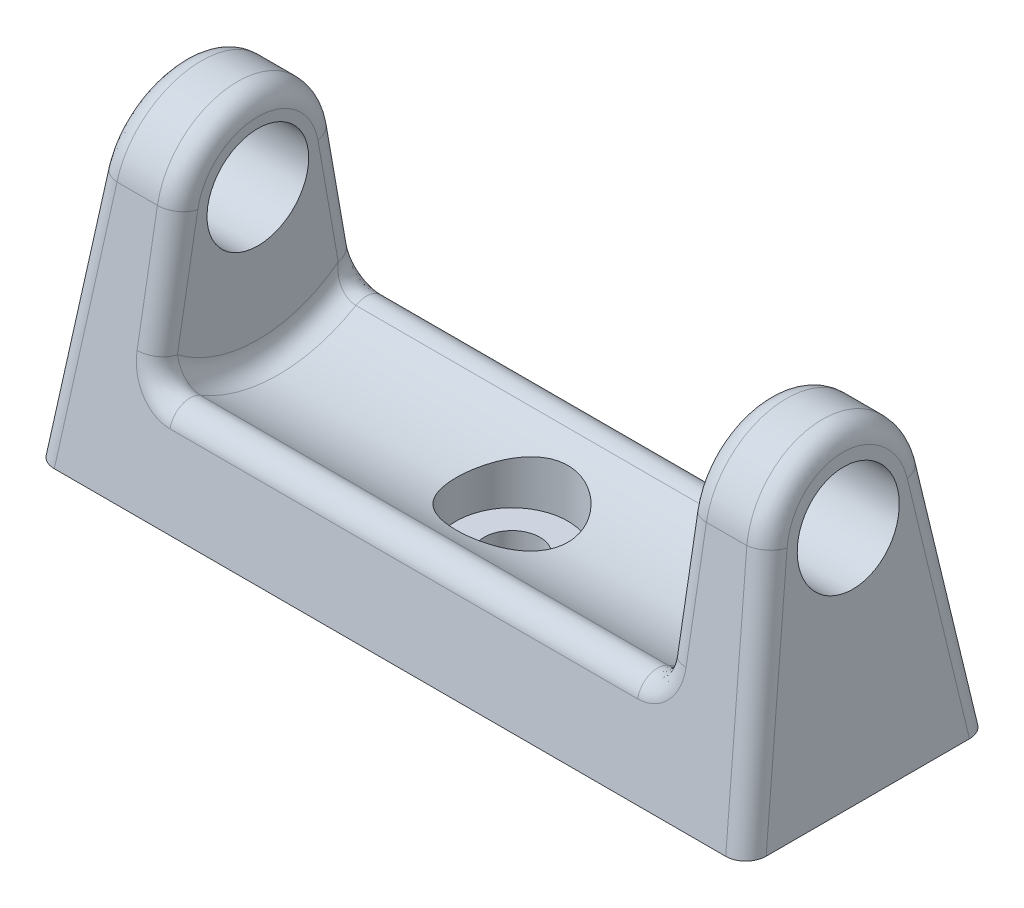
SolidWorks part; units mm, degrees
ref_plane "Front Plane" through (0, 0, 0) normal (0, 0, 1) x (1, 0, 0)
ref_plane "Top Plane" through (0, 0, 0) normal (0, 1, 0) x (1, 0, 0)
ref_plane "Right Plane" through (0, 0, 0) normal (1, 0, 0) x (0, 0, -1)
sketch "Sketch1" plane through (0, 0, 0) normal (1, 0, 0) x (0, 0, -1)
  line L0 (12, 0) -> (-12, 0)
  line L1 (-12, 0) -> (-7.8786, 23.3883)
  line L3 (7.8786, 23.3883) -> (12, 0)
  arc A0 (7.8786, 23.3883) -> (-7.8786, 23.3883) centre (0, 22) ccw
  circle A1 centre (0, 22) radius 5
  point P4 (0, 0)
  dimension "D1" = 22
  dimension "D2" = 10
  dimension "D3" = 16
  dimension "D5" = 24
extrude "Boss-Extrude1" add sketch "Sketch1" along normal mid plane 70
sketch "Sketch2" plane through (0, 0, 0) normal (1, 0, 0) x (0, 0, -1)
  circle A0 centre (0, 22) radius 15
  arc A1 (7.8786, 23.3883) -> (-7.8786, 23.3883) centre (0, 22) ccw construction
  dimension "D1" = 30
extrude "Cut-Extrude1" cut sketch "Sketch2" against normal mid plane 50
fillet "Fillet2" radius 2 10 edges at (25, 7, 0) (-25, 7, 0) (25, 17.1403, -8.9796) (25, 30, 0) (25, 17.1403, 8.9796) (-25, 17.1403, -8.9796) (-25, 30, 0) (-25, 17.1403, 8.9796) (0, 10.8923, 10.0806) (0, 10.8923, -10.0806)
sketch3d "3DSketch2" plane through (0, 0, 0) normal (0, 0, 1) x (1, 0, 0)
sketch "Sketch5" plane through (0, 7, 0) normal (0, -1, 0) x (-1, 0, 0)
  point P0 (0, 0)
sketch "Sketch8" plane through (0, 0, 0) normal (0, 0, 1) x (1, 0, 0)
  line L0 (-35, 30) -> (-35, 0)
  line L1 (-35, 30) -> (-35, 23.3883) construction
  line L2 (-27, 30) -> (-35, 30) construction
  line L3 (-35, 0) -> (-32.3753, 30)
  line L4 (-32.3753, 30) -> (-35, 30)
  line L5 (0, 0) -> (0, 30.0028) construction
  line L6 (35, 0) -> (-35, 0) construction
  line L7 (32.3753, 30) -> (35, 30)
  line L8 (35, 0) -> (32.3753, 30)
  line L9 (35, 30) -> (35, 0)
  point P15 (0, 0)
  dimension "D1" = 5
extrude "Cut-Extrude2" cut sketch "Sketch8" against normal through all both and the other way through all
fillet "Fillet5" radius 2 6 edges at (33.9769, 11.6942, -9.9393) (32.3753, 30, 0) (-33.9769, 11.6942, -9.9393) (-32.3753, 30, 0) (33.9769, 11.6942, 9.9393) (-33.9769, 11.6942, 9.9393)
hole_wizard "CBORE for M5 Pan Head Machine Screw1" positions "3DSketch3" profile "Sketch9" counterbore size "M5" standard "ANSI Metric" end condition up to next
sketch3d "3DSketch3"
  point P0 (0, 7, 0)
sketch "Sketch9" plane through (0, 7, 0) normal (1, 0, 0) x (0, 0, 1)
  line L0 (0, 0) -> (0, 7)
  line L1 (0, 7) -> (2.75, 7)
  line L3 (2.75, 7) -> (2.75, 3.7)
  line L4 (2.75, 3.7) -> (5.5, 3.7)
  line L5 (5.5, 3.7) -> (5.5, 0)
  line L7 (5.5, 0) -> (0, 0)
  line L11 (0, -6.35) -> (0, 107.95) construction
  dimension "Thru Hole Dia." = 5.5
  dimension "Thru Hole Depth" = 7
  dimension "C'Bore Dia." = 11
  dimension "C'Bore Depth" = 3.7
